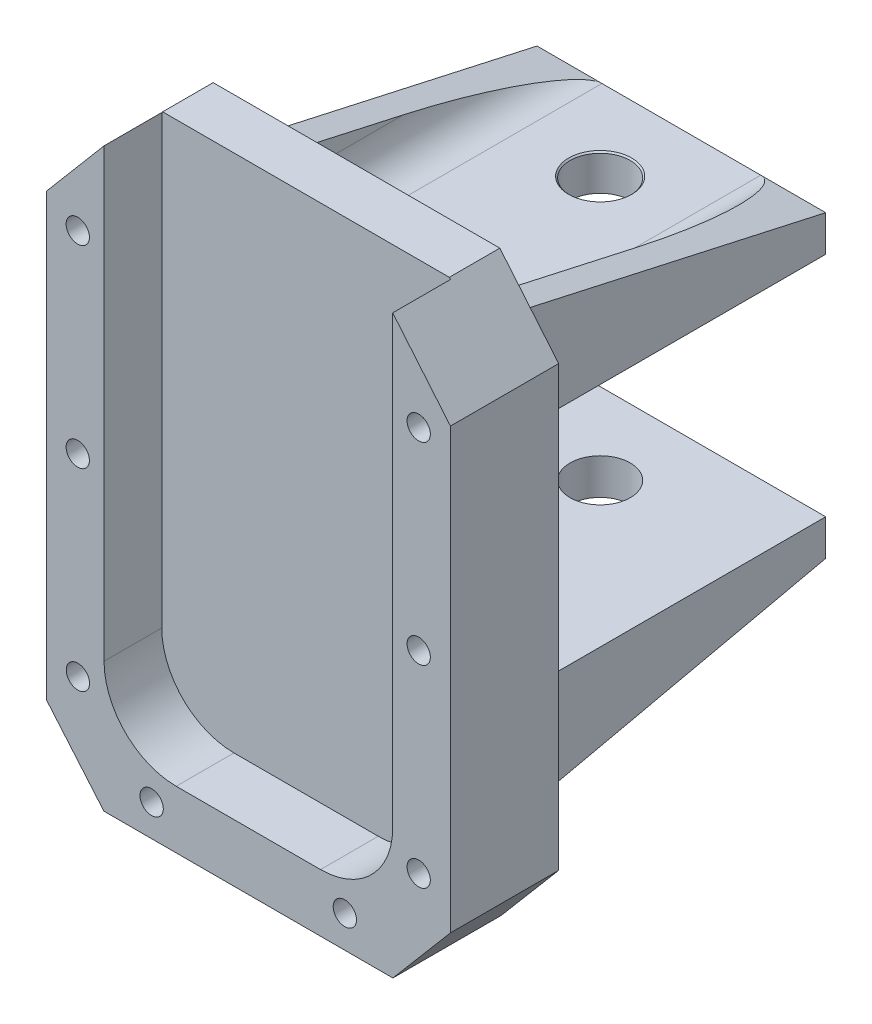
SolidWorks part; units mm, degrees
material "PET"
ref_plane "Front Plane" through (0, 0, 0) normal (0, 0, 1) x (1, 0, 0)
ref_plane "Top Plane" through (0, 0, 0) normal (0, 1, 0) x (1, 0, 0)
ref_plane "Right Plane" through (0, 0, 0) normal (1, 0, 0) x (0, 0, -1)
sketch "Sketch1" plane through (0, 0, 0) normal (0, 0, 1) x (1, 0, 0)
  line L1 (0, 0) -> (-35.56, 0)
  line L2 (0, 0) -> (0, 50.8)
  line L3 (0, 50.8) -> (-35.56, 50.8)
  line L4 (-35.56, 0) -> (-35.56, 50.8)
  dimension "D1" = 50.8
  dimension "D2" = 35.56
extrude "Boss-Extrude1" add sketch "Sketch1" along normal blind 9.525
sketch "Sketch2" plane through (0, 0, 9.525) normal (0, 0, 1) x (1, 0, 0)
  line L0 (0, 50.8) -> (-35.56, 50.8) construction
  line L1 (-30.48, 50.8) -> (-5.08, 50.8)
  line L2 (-30.48, 50.8) -> (-30.48, 5.08)
  line L3 (-30.48, 5.08) -> (-5.08, 5.08)
  line L4 (-5.08, 50.8) -> (-5.08, 5.08)
  line L5 (-35.56, 0) -> (0, 0) construction
  line L6 (-17.78, 0) -> (-17.78, 5.08) construction
  dimension "D1" = 45.72
  dimension "D2" = 25.4
extrude "Cut-Extrude2" cut sketch "Sketch2" against normal blind 5.08
hole_wizard "Tap Drill for M2.5x0.45 Tap1" positions "Sketch6" profile "Sketch5" hole size "M2.5x0.45" standard "ANSI Metric" end condition through all
sketch "Sketch6" plane through (0, 0, 0) normal (0, 0, -1) x (-1, 0, 0)
  point P0 (2.7924, 43.0871)
  point P2 (2.7924, 26.093)
  point P4 (2.7924, 9.1052)
  point P6 (9.2907, 2.8227)
  point P8 (26.2924, 2.7871)
  point P10 (32.78, 9.1052)
  point P12 (32.7924, 26.0871)
  point P14 (32.7924, 43.0871)
sketch "Sketch5" plane through (-2.7924, 43.0871, 0) normal (1, 0, 0) x (0, 1, 0)
  line L0 (0, 0) -> (0, 9.525)
  line L1 (0, 9.525) -> (1.025, 9.525)
  line L2 (1.025, 9.525) -> (1.025, 0)
  line L5 (1.025, 0) -> (0, 0)
  line L11 (0, -6.35) -> (0, 107.95) construction
  dimension "Thru Hole Dia." = 2.05
  dimension "Thru Hole Depth" = 9.525
sketch "Sketch13" plane through (0, 0, 0) normal (0, 0, -1) x (-1, 0, 0)
  line L0 (35.56, 0) -> (0, 0) construction
  line L1 (30.48, 39.265) -> (5.08, 39.265)
  line L2 (30.48, 39.265) -> (30.48, 36.09)
  line L3 (30.48, 36.09) -> (5.08, 36.09)
  line L4 (5.08, 39.265) -> (5.08, 36.09)
  line L5 (30.48, 39.265) -> (5.08, 36.09) construction
  line L6 (30.48, 36.09) -> (5.08, 39.265) construction
  line L7 (30.48, 16.09) -> (5.08, 16.09)
  line L8 (30.48, 16.09) -> (30.48, 12.915)
  line L9 (30.48, 12.915) -> (5.08, 12.915)
  line L10 (5.08, 16.09) -> (5.08, 12.915)
  line L11 (30.48, 16.09) -> (5.08, 12.915) construction
  line L12 (30.48, 12.915) -> (5.08, 16.09) construction
  line L13 (17.78, 16.09) -> (17.78, 36.09) construction
  line L15 (0, 50.8) -> (35.56, 50.8) construction
  point P0 (17.78, 37.6775)
  point P5 (17.78, 14.5025)
  point P12 (17.78, 0)
  point P15 (17.78, 26.09)
  dimension "D1" = 3.175
  dimension "D2" = 3.175
  dimension "D3" = 25.4
  dimension "D4" = 20
  dimension "D5" = 24.71
extrude "Boss-Extrude2" add sketch "Sketch13" along normal blind 28.575
sketch "Sketch8" plane through (0, 0, 9.525) normal (0, 0, 1) x (1, 0, 0)
  line L0 (-5.179, 50.8) -> (0, 44.5915)
  line L1 (-5.08, 50.8) -> (-30.48, 50.8) construction
  line L2 (0, 0) -> (0, 50.8) construction
  line L3 (0.0027, 44.5883) -> (-5.0973, 50.5883) construction
  line L4 (0, 44.5915) -> (0, 50.8)
  line L5 (0, 50.8) -> (-5.179, 50.8)
  line L6 (-35.56, 44.7066) -> (-35.56, 50.8)
  line L7 (-35.56, 50.8) -> (-35.56, 0) construction
  line L8 (-35.56, 50.8) -> (-30.4026, 50.8)
  line L9 (-30.4026, 50.8) -> (-35.56, 44.7066)
  line L10 (-35.56, 5.97) -> (-35.56, 0)
  line L11 (-35.56, 0) -> (-30.4926, 0)
  line L12 (-35.56, 0) -> (0, 0) construction
  line L13 (-30.4926, 0) -> (-35.56, 5.97)
  line L14 (-5.0926, -0.0313) -> (0, 0)
  line L15 (0, 0) -> (0, 5.97)
  line L16 (0, 5.97) -> (-5.0926, -0.0313)
extrude "Cut-Extrude3" cut sketch "Sketch8" against normal through all
ref_plane "Plane6" through (-23.56, 0, 0) normal (-1, 0, 0) x (0, 0, 1)
fillet "Fillet1" radius 6.35 2 edges at (-5.08, 5.08, 6.985) (-30.48, 5.08, 6.985)
sketch "Sketch10" plane through (-43.87, 39.265, 0) normal (0, -1, 0) x (0, 0, -1)
  line L2 (14.2875, 13.39) -> (14.2875, 38.79) construction
  line L3 (0, 38.79) -> (0, 13.39) construction
  line L4 (14.2875, 26.09) -> (0, 26.09) construction
  line L6 (28.575, 13.39) -> (0, 13.39) construction
  line L7 (28.575, 38.79) -> (0, 38.79) construction
  line L8 (14.2875, 26.09) -> (28.575, 26.09) construction
  line L9 (28.575, 38.79) -> (28.575, 13.39) construction
  circle A0 centre (21.4312, 26.09) radius 3.175
  circle A1 centre (7.1438, 26.09) radius 3.175
  point P10 (23.8125, 26.09)
  dimension "D1" = 6.35
hole_wizard "M5 Clearance Hole1" positions "3DSketch1" profile "Sketch11" hole size "M5" standard "ANSI Metric" end condition through all
sketch3d "3DSketch1"
  point P0 (-17.78, 39.265, -7.1438)
  point P3 (-17.78, 39.265, -21.4312)
sketch "Sketch11" plane through (-17.78, 39.265, -7.1438) normal (1, 0, 0) x (0, 0, 1)
  line L0 (0, 0) -> (0, 39.265)
  line L1 (0, 39.265) -> (2.65, 39.265)
  line L2 (2.65, 39.265) -> (2.65, 0.125)
  line L3 (2.65, 0.125) -> (2.775, 0)
  line L5 (2.775, 0) -> (0, 0)
  line L6 (-2.65, 0.125) -> (-2.775, 0) construction
  line L11 (0, -6.35) -> (0, 107.95) construction
  dimension "Thru Hole Dia." = 5.3
  dimension "Thru Hole Depth" = 39.265
  dimension "Near C'Sink Dia." = 5.55
  dimension "Near C'Sink Angle" = 90
sketch "Sketch14" plane through (-30.48, 0, 0) normal (-1, 0, 0) x (0, 0, 1)
  line L0 (-28.575, 12.915) -> (0, 6.565)
  line L1 (0, 44.7066) -> (0, 5.97) construction
  line L2 (-28.575, 12.915) -> (0, 12.915) construction
  point P5 (0, 0)
  dimension "D1" = 6.35
rib "Rib7" sketch "Sketch14" sketch "Sketch14" thickness 2.54 extrusion direction parallel to sketch draft on no parameters "D1"=2.54
sketch "Sketch15" plane through (-5.08, 0, 0) normal (1, 0, 0) x (0, 0, -1)
  line L0 (28.575, 12.915) -> (0, 6.565)
rib "Rib8" sketch "Sketch15" sketch "Sketch15" thickness 2.54 extrusion direction parallel to sketch draft on no parameters "D1"=2.54
sketch "Sketch16" plane through (-30.48, 0, 0) normal (-1, 0, 0) x (0, 0, 1)
  line L0 (-28.575, 39.265) -> (0, 45.615)
  line L1 (0, 44.7066) -> (0, 5.97) construction
  point P5 (0, 0)
  point P8 (0, 0)
  point P11 (0, 0)
  dimension "D1" = 6.35
sketch "Sketch17" plane through (-5.08, 0, 0) normal (1, 0, 0) x (0, 0, -1)
  line L0 (28.575, 39.265) -> (0, 45.615)
rib "Rib9" sketch "Sketch17" sketch "Sketch17" thickness 2.54 extrusion direction parallel to sketch draft on no parameters "D1"=2.54
rib "Rib10" sketch "Sketch16" sketch "Sketch16" thickness 2.54 extrusion direction parallel to sketch draft on no parameters "D1"=2.54
fillet "Fillet2" radius 3.175 2 edges at (-27.94, 12.915, -14.2875) (-7.62, 12.915, -14.2875)
fillet "Fillet3" radius 3.175 2 edges at (-7.62, 39.265, -14.2875) (-27.94, 39.265, -14.2875)
